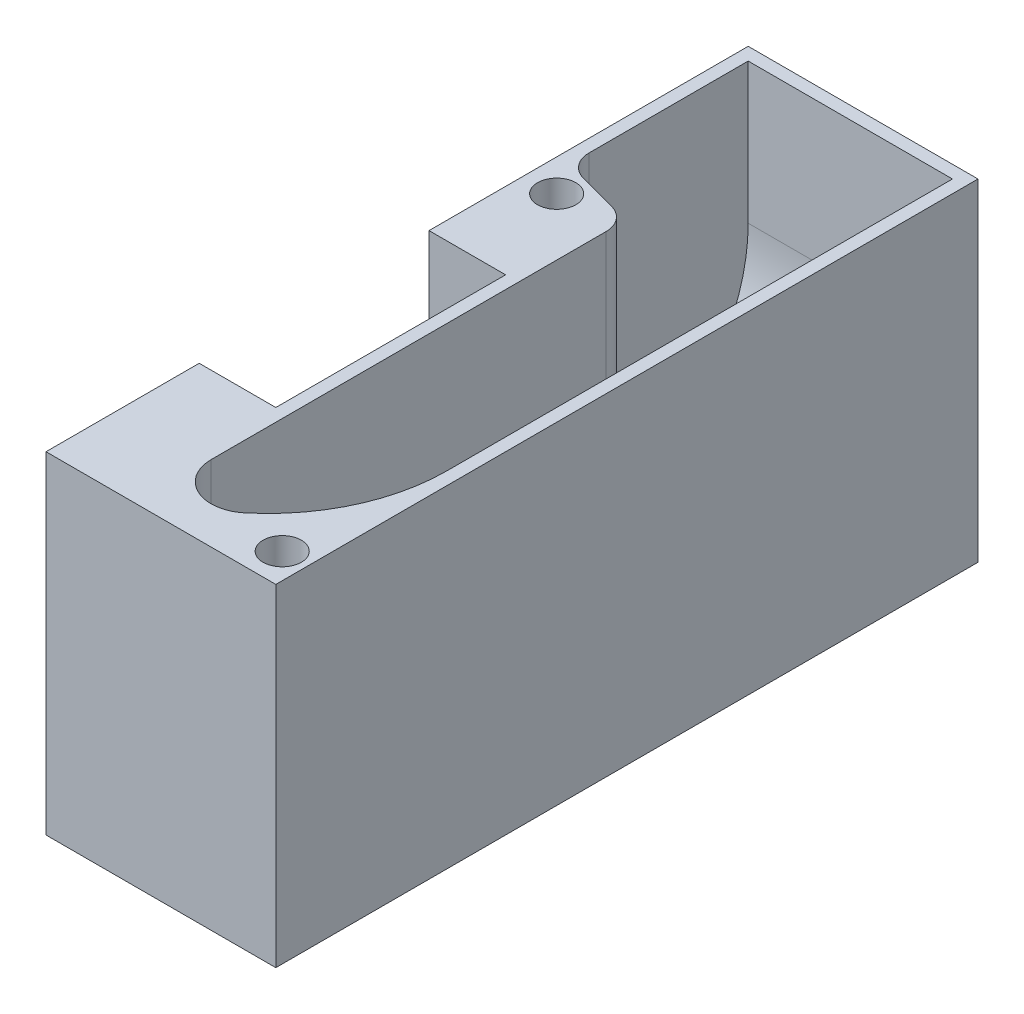
SolidWorks part; units mm, degrees
ref_plane "Front Plane" through (0, 0, 0) normal (0, 0, 1) x (1, 0, 0)
ref_plane "Top Plane" through (0, 0, 0) normal (0, 1, 0) x (1, 0, 0)
ref_plane "Right Plane" through (0, 0, 0) normal (1, 0, 0) x (0, 0, -1)
sketch "Sketch2" plane through (0, 0, 0) normal (0, -1, 0) x (1, 0, 0)
  line L0 (0, 0) -> (13, 0) construction
  line L18 (7, -10) -> (7, -35)
  line L20 (7, -35) -> (25, -35)
  line L21 (25, -35) -> (25, 20)
  line L22 (25, 20) -> (7, 20)
  line L23 (7, 20) -> (7, 8)
  line L24 (7, 8) -> (13, 8)
  line L25 (13, 8) -> (13, -10)
  line L26 (13, -10) -> (7, -10)
  dimension "D1" = 13
  dimension "D2" = 18
  dimension "D3" = 25
  dimension "D4" = 20
  dimension "D5" = 7
  dimension "D6" = 55
  dimension "D7" = 10
extrude "Boss-Extrude2" add sketch "Sketch2" along normal blind 26 separate body
shell "Shell1" thickness 1 removed face at (13, 0, -4.25)
fillet "Fillet1" radius 14 1 edges at (16, -25, -34)
sketch "Sketch3" plane through (0, 0, 0) normal (0, 1, 0) x (1, 0, 0)
  line L0 (14, 11) -> (8, 11)
  line L1 (8, 11) -> (8, 20)
  line L2 (8, 20) -> (14, 18.3923)
  line L3 (14, 18.3923) -> (14, 11)
  line L4 (24, 20) -> (8, 20) construction
  line L5 (14, -9) -> (8, -9)
  line L6 (14, -9) -> (14, -19)
  line L7 (14, -19) -> (8, -19)
  line L8 (8, -9) -> (8, -19)
  line L9 (11, -19) -> (11, -9) construction
  line L10 (14, -14) -> (8, -14) construction
  line L11 (8, 11) -> (8, 20) construction
  point P139 (11, -14)
  dimension "D1" = 75
extrude "Boss-Extrude3" add sketch "Sketch3" against normal up to next
fillet "Fillet2" radius 14 1 edges at (24, -12.5, 19)
sketch "Sketch7" plane through (0, 0, 0) normal (0, 1, 0) x (1, 0, 0)
  line L0 (9.5, 17.5) -> (9.5, -17.5) construction
  line L1 (9.5, -17.5) -> (23, -17.5) construction
  line L2 (0, 0) -> (9.5, 0) construction
  circle A0 centre (23, -17.5) radius 1.5
  circle A1 centre (9.5, 17.5) radius 1.5
  dimension "D4" = 3
  dimension "D1" = 9.5
  dimension "D2" = 35
  dimension "D3" = 13.5
extrude "Cut-Extrude2" cut sketch "Sketch7" against normal blind 3
fillet "Fillet3" radius 3 1 edges at (14, -12.5, 19)
fillet "Fillet4" [suppressed] radius 2
fillet "Fillet5" radius 2 2 edges at (14, -12.5, -18.3923) (8, -12.5, -20)
sketch "Sketch4" plane through (7, 0, 0) normal (-1, 0, 0) x (0, 0, 1)
  line L0 (11.5, -23) -> (-13.5, -23) construction
  line L1 (-1, -26) -> (-1, -23) construction
  line L4 (8, -26) -> (-10, -26) construction
  circle A0 centre (-13.5, -23) radius 2
  circle A1 centre (11.5, -23) radius 2
  dimension "D1" = 4
  dimension "D2" = 25
  dimension "D3" = 3
extrude "Cut-Extrude1" cut sketch "Sketch4" against normal blind 9
